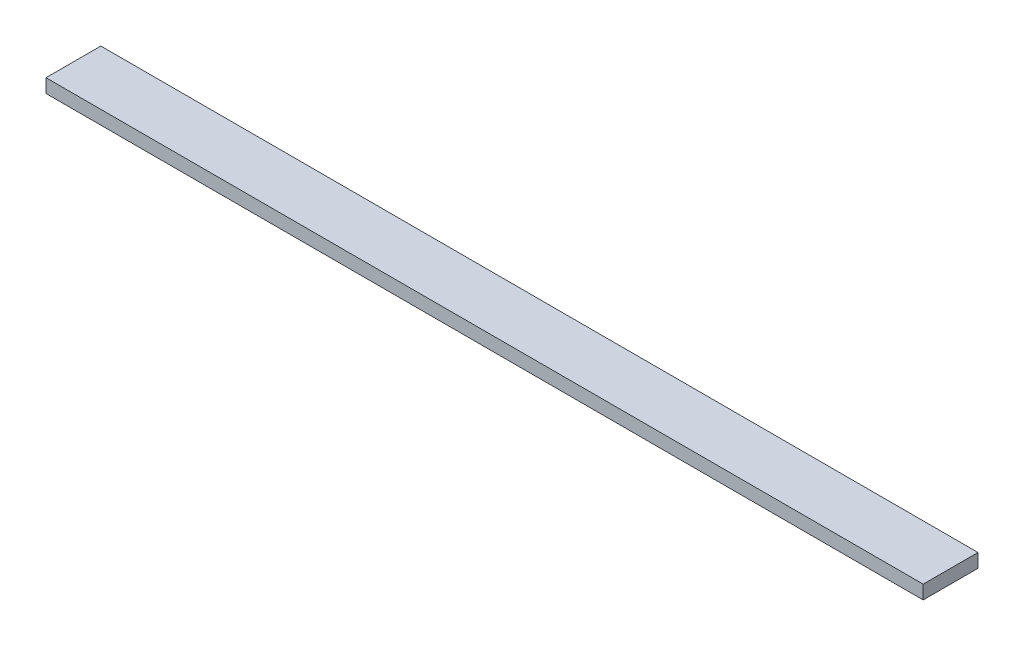
SolidWorks part; units mm, degrees
ref_plane "Front Plane" through (0, 0, 0) normal (0, 0, 1) x (1, 0, 0)
ref_plane "Top Plane" through (0, 0, 0) normal (0, 1, 0) x (1, 0, 0)
ref_plane "Right Plane" through (0, 0, 0) normal (1, 0, 0) x (0, 0, -1)
sketch "Sketch1" plane through (0, 0, 0) normal (0, 1, 0) x (1, 0, 0)
  line L1 (0, 0) -> (406.4, 0)
  line L2 (0, 0) -> (0, 25.4)
  line L3 (0, 25.4) -> (406.4, 25.4)
  line L4 (406.4, 0) -> (406.4, 25.4)
  dimension "D1" = 25.4
  dimension "D2" = 406.4
extrude "Boss-Extrude1" add sketch "Sketch1" along normal blind 6.35
